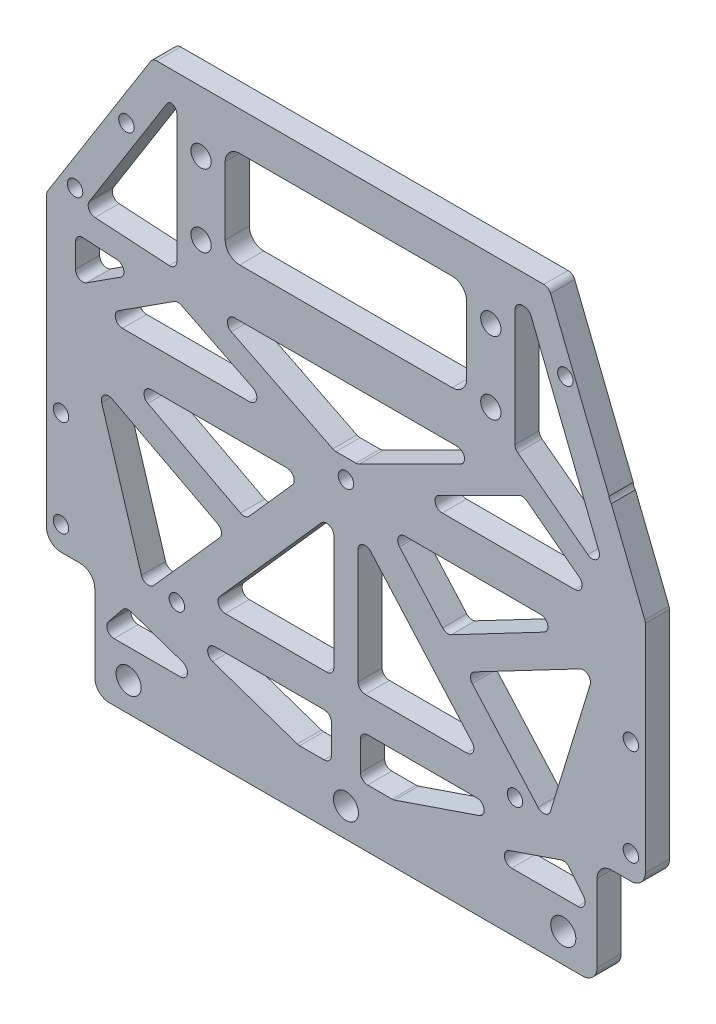
SolidWorks part; units mm, degrees
material "Thornel Mat VMA"
ref_plane "前视基准面" through (0, 0, 0) normal (0, 0, 1) x (1, 0, 0)
ref_plane "上视基准面" through (0, 0, 0) normal (0, 1, 0) x (1, 0, 0)
ref_plane "右视基准面" through (0, 0, 0) normal (1, 0, 0) x (0, 0, -1)
sketch "草图1" plane through (0, 0, 0) normal (0, 0, 1) x (1, 0, 0)
  line L1 (-62, 60) -> (62, 60)
  line L2 (-62, 60) -> (-62, -60)
  line L3 (-62, -60) -> (62, -60)
  line L4 (62, 60) -> (62, -60)
  line L5 (-62, 60) -> (62, -60) construction
  line L6 (-62, -60) -> (62, 60) construction
  point P0 (0, 0)
  dimension "D1" = 124
  dimension "D2" = 120
extrude "凸台-拉伸1" add sketch "草图1" along normal blind 5
sketch "草图2" plane through (0, 0, 5) normal (0, 0, 1) x (1, 0, 0)
  line L0 (-35, -35) -> (35, -35) construction
  line L1 (-62, -60) -> (62, -60) construction
  circle A0 centre (-35, -35) radius 1.6
  circle A1 centre (35, -35) radius 1.6
  point P2 (0, -35)
  dimension "D3" = 3.2
  dimension "D1" = 70
  dimension "D2" = 25
extrude "切除-拉伸1" cut sketch "草图2" against normal through all
sketch "草图3" plane through (0, 0, 5) normal (0, 0, 1) x (1, 0, 0)
  circle A0 centre (0, 4.5) radius 1.6
  circle A1 centre (35, -35) radius 1.6 construction
  dimension "D1" = 3.2
  dimension "D2" = 39.5
extrude "切除-拉伸2" cut sketch "草图3" against normal through all
sketch "草图4" plane through (0, 0, 5) normal (0, 0, 1) x (1, 0, 0)
  line L1 (-30, 47.5) -> (30, 47.5) construction
  line L2 (-30, 47.5) -> (-30, 32.5) construction
  line L3 (-30, 32.5) -> (30, 32.5) construction
  line L4 (30, 47.5) -> (30, 32.5) construction
  line L5 (-30, 47.5) -> (30, 32.5) construction
  line L6 (-30, 32.5) -> (30, 47.5) construction
  circle A0 centre (-30, 47.5) radius 2.1
  circle A1 centre (30, 32.5) radius 2.1
  circle A2 centre (30, 47.5) radius 2.1
  circle A3 centre (-30, 32.5) radius 2.1
  point P0 (0, 40)
  dimension "D4" = 4.2
  dimension "D1" = 40
  dimension "D2" = 15
  dimension "D3" = 60
extrude "切除-拉伸3" cut sketch "草图4" against normal through all
chamfer "倒角1" distance 22 distance2 35 1 edges at (-62, 60, 2.5) first distance on face at (0, 60, 2.5)
chamfer "倒角2" distance 50 distance2 20 1 edges at (62, 60, 2.5) first distance on face at (62, 0, 2.5)
sketch "草图7" plane through (0, 0, 5) normal (0, 0, 1) x (1, 0, 0)
  line L0 (-45, -54) -> (45, -54) construction
  line L1 (-62, -60) -> (62, -60) construction
  circle A0 centre (-45, -54) radius 2.6
  circle A1 centre (0, -54) radius 2.6
  circle A2 centre (45, -54) radius 2.6
  point P4 (0, -54)
  dimension "D3" = 5.2
  dimension "D1" = 6
  dimension "D2" = 90
extrude "切除-拉伸4" cut sketch "草图7" against normal through all
sketch "草图8" plane through (0, 0, 0) normal (0, 0, -1) x (-1, 0, 0)
  circle A0 centre (-59, -33) radius 1.6
  circle A1 centre (-59, -13) radius 1.6
  circle A2 centre (45.4427, 45.7039) radius 1.6
  circle A3 centre (56.0861, 28.7712) radius 1.6
  circle A4 centre (30, 47.5) radius 2.1 construction
  dimension "D1" = 3.2
  dimension "D2" = 45.4427
  dimension "D3" = 56.0861
  dimension "D4" = 59
  dimension "D5" = 28.7712
  dimension "D6" = 45.7039
  dimension "D7" = 13
  dimension "D8" = 33
extrude "切除-拉伸5" cut sketch "草图8" against normal through all
sketch "草图9" plane through (0, 0, 5) normal (0, 0, 1) x (1, 0, 0)
  line L6 (0, 4.5) -> (-35, -35)
  line L7 (25, 52) -> (-25, 52)
  line L8 (25, 52) -> (25, 32)
  line L9 (25, 32) -> (-25, 32)
  line L10 (-25, 52) -> (-25, 32)
  line L11 (25, 52) -> (-25, 32) construction
  line L12 (56, -54) -> (56, 8.8445)
  line L13 (56, 8.8445) -> (37.9378, 54)
  line L14 (37.9378, 54) -> (-36.6846, 54)
  line L15 (-36.6846, 54) -> (-56, 23.2709)
  line L16 (-56, 23.2709) -> (-56, -54)
  line L17 (-56, -54) -> (56, -54)
  line L18 (56, -54) -> (56, 8.8445)
  line L19 (56, 8.8445) -> (37.9378, 54)
  line L20 (37.9378, 54) -> (-36.6846, 54)
  line L21 (-36.6846, 54) -> (-56, 23.2709)
  line L22 (-56, 23.2709) -> (-56, -54)
  line L23 (-56, -54) -> (56, -54)
  line L24 (25, 32) -> (-25, 52) construction
  line L25 (-35, -35) -> (35, -35)
  line L26 (35, -35) -> (0, 4.5)
  line L27 (43.8887, -39) -> (1.8, 8.5)
  line L28 (-1.8, 8.5) -> (-43.8887, -39)
  line L29 (-43.8887, -39) -> (43.8887, -39)
  line L30 (28.3335, -32) -> (0, -0.0236)
  line L31 (0, -0.0236) -> (-28.3335, -32)
  line L32 (-28.3335, -32) -> (28.3335, -32)
  line L33 (56, 4.5) -> (-56, 4.5)
  line L34 (56, 8.5) -> (-56, 8.5)
  line L35 (56, 0.5) -> (-56, 0.5)
  line L36 (43.8887, -39) -> (56, 0.5)
  line L37 (43.8887, -39) -> (56, -54)
  line L38 (-56, 0.5) -> (-43.8887, -39)
  line L39 (-56, -54) -> (-43.8887, -39)
  line L40 (-58.8682, -0.3794) -> (-47.2241, -38.3555)
  line L41 (47.2241, -38.3555) -> (56, -48)
  line L42 (-47.2241, -38.3555) -> (-56, -48)
  line L43 (47.2241, -38.3555) -> (58.8682, -0.3794)
  line L44 (-53.1318, 1.3794) -> (-40.5532, -39.6445)
  line L45 (36.118, 19.7639) -> (39.1448, 21.2773)
  line L46 (-52.8621, 0.5) -> (-22.8444, -15.25)
  line L47 (40.5532, -39.6445) -> (53.1318, 1.3794)
  line L48 (35, 22) -> (-35, 22)
  line L49 (-35, 62) -> (-35, 22)
  line L50 (35, 62) -> (-35, 62)
  line L51 (35, 62) -> (35, 22)
  line L52 (25, 32) -> (56, 8.5)
  line L53 (-35, 22) -> (-56, 23.2709)
  line L54 (-35, 22) -> (-56, 8.5)
  line L55 (-27.2138, 24.0334) -> (-54.6481, 6.3971)
  line L56 (-27.2138, 24.0334) -> (-55.849, 25.7663)
  line L57 (-42.7862, 19.9666) -> (-57.3519, 10.6029)
  line L58 (-42.7862, 19.9666) -> (-56.151, 20.7755)
  line L59 (35, 22) -> (0, 4.5)
  line L60 (-35, 22) -> (0, 4.5)
  line L61 (23.4897, 30.0077) -> (54.4897, 6.5077)
  line L62 (33.882, 24.2361) -> (0, 7.2951)
  line L63 (-33.882, 24.2361) -> (0, 7.2951)
  line L64 (26.5103, 33.9923) -> (57.5103, 10.4923)
  line L65 (36.118, 19.7639) -> (0, 1.7049)
  line L66 (-36.118, 19.7639) -> (0, 1.7049)
  line L67 (0, -0.0236) -> (0, -32)
  line L68 (-2.5, -0.0236) -> (-2.5, -32)
  line L69 (2.5, -0.0236) -> (2.5, -32)
  line L70 (43.8887, -39) -> (0, -54)
  line L71 (0, -54) -> (-43.8887, -39)
  line L72 (43.0801, -36.6344) -> (0, -51.358)
  line L73 (0, -51.358) -> (-43.0801, -36.6344)
  line L74 (52.8621, 0.5) -> (22.8444, -15.25)
  line L75 (51.4683, 3.1565) -> (21.4505, -12.5935)
  line L76 (-56, -48) -> (56, -48)
  line L77 (-54.256, -2.1565) -> (-24.2382, -17.9065)
  line L78 (54.256, -2.1565) -> (24.2382, -17.9065)
  line L79 (-53.6659, -55.8846) -> (-40.5532, -39.6445) construction
  line L80 (40.5532, -39.6445) -> (53.6659, -55.8846) construction
  line L81 (-51.4683, 3.1565) -> (-21.4505, -12.5935)
  line L82 (21.4505, -12.5935) -> (20.7951, -12.9373)
  line L83 (-21.4505, -12.5935) -> (-20.7951, -12.9373)
  line L84 (43.8887, -39) -> (0, 10.5315) construction
  line L85 (0, 10.5315) -> (-43.8887, -39) construction
  line L86 (44.6972, -41.3656) -> (0, -56.642)
  line L87 (0, -56.642) -> (-44.6972, -41.3656)
  line L88 (-44.6972, -41.3656) -> (-45.5605, -41.0706)
  line L89 (44.6972, -41.3656) -> (45.5605, -41.0706)
  line L90 (0, -48) -> (0, -39)
  line L91 (3, -48) -> (3, -39)
  line L92 (-3, -48) -> (-3, -39)
  line L99 (-58.3341, -52.1154) -> (-47.2241, -38.3555) construction
  line L100 (47.2241, -38.3555) -> (58.3341, -52.1154) construction
  point P0 (0, 42)
  dimension "D2" = 42
  dimension "D3" = 20
  dimension "D4" = 50
  dimension "D1" = 6
  dimension "D5" = 4
  dimension "D6" = 3
  dimension "D7" = 4
  dimension "D8" = 4
  dimension "D9" = 3
  dimension "D10" = 3
  dimension "D11" = 10
  dimension "D12" = 2.5
  dimension "D13" = 2.5
  dimension "D14" = 2.5
  dimension "D15" = 2.5
  dimension "D16" = 2.5
  dimension "D17" = 2.5
  dimension "D18" = 2.5
  dimension "D19" = 3
  dimension "D20" = 6
  dimension "D21" = 3
  dimension "D22" = 2.5
  dimension "D23" = 3
  dimension "D24" = 3
extrude "切除-拉伸6" cut sketch "草图9" against normal blind 10 contours L51 L64 L19 L20 | L7 L10 L9 L8 | L56 L49 L20 L21 | L57 L58 L22 | L48 L63 L34 L28 L27 L62 | L45 L65 L34 L61 | L66 L55 L34 | L35 L44 L28 | L27 L47 L35 | L30 L69 L32 | L68 L31 L32 | L22 L76 L40 | L81 L83 L28 L35 | L82 L75 L35 L27 | L76 L92 L29 L73 | L91 L76 L72 L29 | L89 L86 L76 L37 | L87 L88 L39 L76 | L76 L18 L43 region at (-25.363, -3.9791, 5) region at (25.363, -3.9791, 5) region at (34.0343, 12.3435, 5) region at (-33.2707, 12.0425, 5) region at (0, 17.1592, 5) region at (0, 42, 5) region at (53.0747, -32.0298, 5) region at (-51.5954, 17.4017, 5) region at (-53.0747, -32.0298, 5) region at (-41.5375, 35.483, 5) region at (-39.3584, -19.1564, 5) region at (39.3584, -19.1564, 5) region at (40.6672, -45.6902, 5) region at (41.6524, 33.1508, 5) region at (-40.6672, -45.6902, 5) region at (14.4412, -42.5121, 5) region at (-14.4412, -42.5121, 5) region at (11.1112, -22.2817, 5) region at (-11.1112, -22.2817, 5)
fillet "圆角2" radius 1.5 65 edges at (-56, -48, 2.5) (-56, -9.7338, 2.5) (-47.2241, -38.3555, 2.5) (3, -39, 2.5) (36.1585, -39, 2.5) (9.8253, -48, 2.5) (3, -48, 2.5) (20.7951, -12.9373, 2.5) (8.8887, 0.5, 2.5) (46.4052, 0.5, 2.5) (-56, 11.472, 2.5) (-56, 20.7663, 2.5) (-42.7862, 19.9666, 2.5) (2.4098, 8.5, 2.5) (-2.4098, 8.5, 2.5) (-29.4098, 22, 2.5) (29.4098, 22, 2.5) (-13.5902, 8.5, 2.5) (-51.3769, 8.5, 2.5) (-34.8452, 19.1275, 2.5) (56, -9.7338, 2.5) (56, -48, 2.5) (47.2241, -38.3555, 2.5) (37.9378, 54, 2.5) (54.3968, 12.8525, 2.5) (35, 27.5565, 2.5) (35, 54, 2.5) (-40, 60, 2.5) (-62, 25, 2.5) (-62, -60, 2.5) (62, -60, 2.5) (62, 10, 2.5) (42, 60, 2.5) (-51.1555, -48, 2.5) (-45.5605, -41.0706, 2.5) (-25.2857, -48, 2.5) (24.8936, -17.5627, 2.5) (51.6242, -3.5374, 2.5) (41.5575, -36.3691, 2.5) (-24.8936, -17.5627, 2.5) (-41.5575, -36.3691, 2.5) (-51.6242, -3.5374, 2.5) (36.6512, 20.0305, 2.5) (51.8616, 8.5, 2.5) (13.5902, 8.5, 2.5) (-54.4834, 25.6837, 2.5) (-36.6846, 54, 2.5) (-35, 54, 2.5) (-35, 24.5046, 2.5) (-36.1585, -39, 2.5) (-3, -39, 2.5) (-3, -48, 2.5) (-9.8253, -48, 2.5) (45.5605, -41.0706, 2.5) (51.1555, -48, 2.5) (25.2857, -48, 2.5) (2.5, -32, 2.5) (2.5, -2.845, 2.5) (28.3335, -32, 2.5) (-2.5, -32, 2.5) (-28.3335, -32, 2.5) (-2.5, -2.845, 2.5) (-8.8887, 0.5, 2.5) (-20.7951, -12.9373, 2.5) (-46.4052, 0.5, 2.5)
fillet "圆角3" radius 3 4 edges at (25, 32, 2.5) (-25, 52, 2.5) (25, 52, 2.5) (-25, 32, 2.5)
mirror "镜向1" about plane through (0, 0, 0) normal (1, 0, 0) of "切除-拉伸5"
sketch "草图11" plane through (0, 0, 5) normal (0, 0, 1) x (1, 0, 0)
  line L0 (47.4747, -37.5384) -> (53.0659, -19.3031) construction
  line L1 (47.7993, -38.9877) -> (53.3906, -45.1323) construction
  line L2 (56, -44.1228) -> (56, -19.7428) construction
  line L3 (47.4747, -37.5384) -> (53.0659, -19.3031)
  line L4 (47.7993, -38.9877) -> (53.3906, -45.1323)
  line L5 (56, -44.1228) -> (56, -19.7428)
  line L6 (0, -54) -> (0, 10.2215) construction
  line L7 (-56, -44.1228) -> (-56, -19.7428)
  line L8 (-47.7993, -38.9877) -> (-53.3906, -45.1323)
  line L9 (-47.4747, -37.5384) -> (-53.0659, -19.3031)
  arc A0 (56, -19.7428) -> (53.0659, -19.3031) centre (54.5, -19.7428) ccw construction
  arc A1 (47.4747, -37.5384) -> (47.7993, -38.9877) centre (48.9088, -37.9781) ccw construction
  arc A2 (53.3906, -45.1323) -> (56, -44.1228) centre (54.5, -44.1228) ccw construction
  arc A3 (56, -19.7428) -> (53.0659, -19.3031) centre (54.5, -19.7428) ccw
  arc A4 (47.4747, -37.5384) -> (47.7993, -38.9877) centre (48.9088, -37.9781) ccw
  arc A5 (53.3906, -45.1323) -> (56, -44.1228) centre (54.5, -44.1228) ccw
  arc A6 (-53.3906, -45.1323) -> (-56, -44.1228) centre (-54.5, -44.1228) cw
  arc A7 (-47.4747, -37.5384) -> (-47.7993, -38.9877) centre (-48.9088, -37.9781) cw
  arc A8 (-56, -19.7428) -> (-53.0659, -19.3031) centre (-54.5, -19.7428) cw
extrude "凸台-拉伸2" add sketch "草图11" against normal up to surface (5 mm away) up to face at (-57.4, -33, 0)
sketch "草图10" plane through (0, 0, 0) normal (0, 0, -1) x (-1, 0, 0)
  line L3 (-62, -58.5) -> (-62, 9.7111) construction
  line L5 (60.5, -60) -> (-60.5, -60) construction
  line L6 (-62, -58.5) -> (-62, -38)
  line L7 (-62, -38) -> (-52, -38)
  line L8 (-52, -38) -> (-52, -60)
  line L9 (0, 0) -> (0, -75.6001) construction
  line L10 (-52, -60) -> (-60.5, -60)
  line L11 (52, -60) -> (60.5, -60)
  line L12 (52, -38) -> (52, -60)
  line L13 (62, -38) -> (52, -38)
  line L14 (62, -58.5) -> (62, -38)
  arc A1 (-62, -58.5) -> (-60.5, -60) centre (-60.5, -58.5) ccw construction
  arc A3 (-62, -58.5) -> (-60.5, -60) centre (-60.5, -58.5) ccw
  arc A4 (62, -58.5) -> (60.5, -60) centre (60.5, -58.5) cw
  dimension "D1" = 22
  dimension "D2" = 10
extrude "切除-拉伸7" cut sketch "草图10" against normal through all
fillet "圆角4" radius 3 6 edges at (62, -38, 2.5) (52, -38, 2.5) (52, -60, 2.5) (-52, -60, 2.5) (-52, -38, 2.5) (-62, -38, 2.5)
